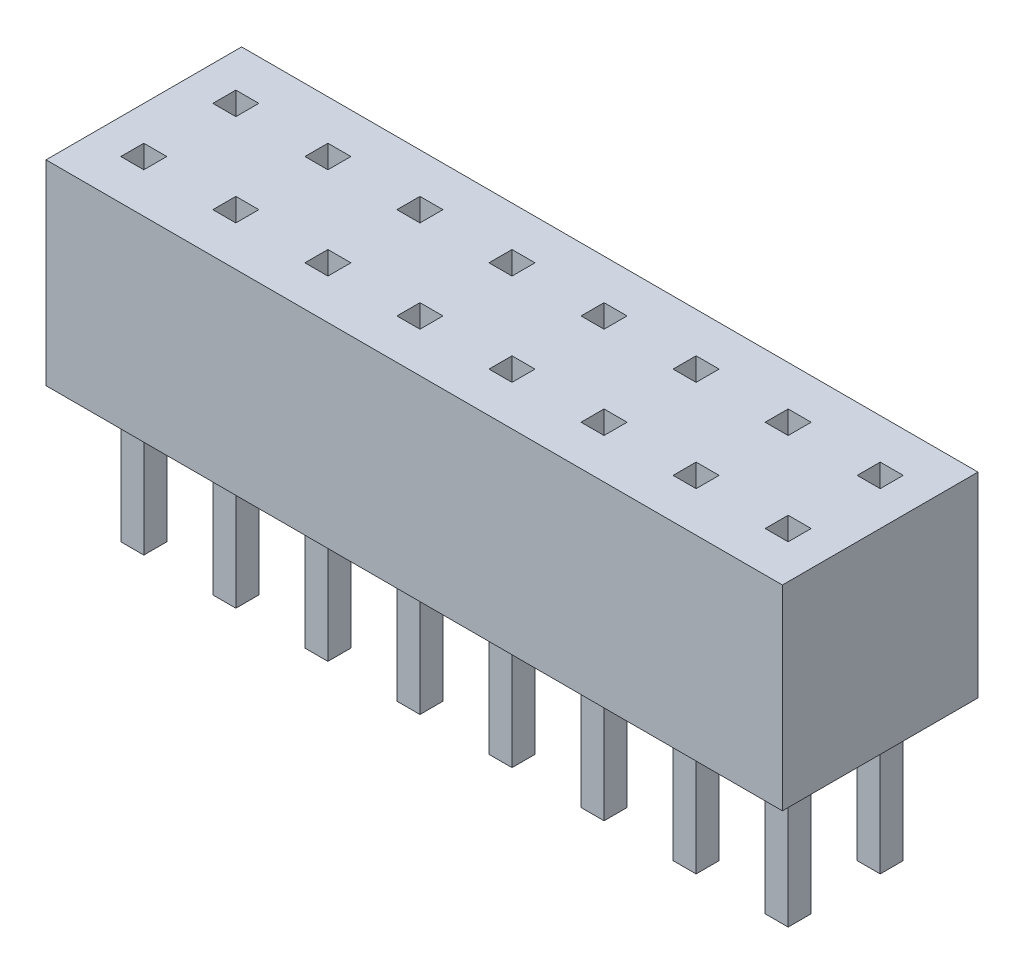
SolidWorks part; units mm, degrees
ref_plane "Front Plane" through (0, 0, 0) normal (0, 0, 1) x (1, 0, 0)
ref_plane "Top Plane" through (0, 0, 0) normal (0, 1, 0) x (1, 0, 0)
ref_plane "Right Plane" through (0, 0, 0) normal (1, 0, 0) x (0, 0, -1)
sketch "Sketch1" plane through (0, 0, 0) normal (0, 1, 0) x (1, 0, 0)
  line L1 (0, 0) -> (16, 0)
  line L2 (0, 0) -> (0, -4.25)
  line L3 (0, -4.25) -> (16, -4.25)
  line L4 (16, 0) -> (16, -4.25)
extrude "Boss-Extrude1" add sketch "Sketch1" along normal blind 4.25
sketch "Sketch3" plane through (0, 0, 0) normal (0, -1, 0) x (1, 0, 0)
  line L0 (2.75, 0.875) -> (3.25, 0.875)
  line L1 (0.75, 0.875) -> (1.25, 0.875)
  line L2 (0.75, 0.875) -> (0.75, 1.375)
  line L3 (0.75, 1.375) -> (1.25, 1.375)
  line L4 (1.25, 0.875) -> (1.25, 1.375)
  line L5 (2.75, 0.875) -> (2.75, 1.375)
  line L6 (2.75, 1.375) -> (3.25, 1.375)
  line L7 (3.25, 0.875) -> (3.25, 1.375)
  line L8 (4.75, 0.875) -> (5.25, 0.875)
  line L9 (4.75, 0.875) -> (4.75, 1.375)
  line L10 (4.75, 1.375) -> (5.25, 1.375)
  line L11 (5.25, 0.875) -> (5.25, 1.375)
  line L12 (6.75, 0.875) -> (7.25, 0.875)
  line L13 (6.75, 0.875) -> (6.75, 1.375)
  line L14 (6.75, 1.375) -> (7.25, 1.375)
  line L15 (7.25, 0.875) -> (7.25, 1.375)
  line L16 (8.75, 0.875) -> (9.25, 0.875)
  line L17 (8.75, 0.875) -> (8.75, 1.375)
  line L18 (8.75, 1.375) -> (9.25, 1.375)
  line L19 (9.25, 0.875) -> (9.25, 1.375)
  line L20 (10.75, 0.875) -> (11.25, 0.875)
  line L21 (10.75, 0.875) -> (10.75, 1.375)
  line L22 (10.75, 1.375) -> (11.25, 1.375)
  line L23 (11.25, 0.875) -> (11.25, 1.375)
  line L24 (12.75, 0.875) -> (13.25, 0.875)
  line L25 (12.75, 0.875) -> (12.75, 1.375)
  line L26 (12.75, 1.375) -> (13.25, 1.375)
  line L27 (13.25, 0.875) -> (13.25, 1.375)
  line L28 (14.75, 0.875) -> (15.25, 0.875)
  line L29 (14.75, 0.875) -> (14.75, 1.375)
  line L30 (14.75, 1.375) -> (15.25, 1.375)
  line L31 (15.25, 0.875) -> (15.25, 1.375)
  line L72 (0.75, 2.875) -> (1.25, 2.875)
  line L73 (0.75, 2.875) -> (0.75, 3.375)
  line L74 (0.75, 3.375) -> (1.25, 3.375)
  line L75 (1.25, 2.875) -> (1.25, 3.375)
  line L76 (2.75, 2.875) -> (3.25, 2.875)
  line L77 (2.75, 2.875) -> (2.75, 3.375)
  line L78 (2.75, 3.375) -> (3.25, 3.375)
  line L79 (3.25, 2.875) -> (3.25, 3.375)
  line L80 (4.75, 2.875) -> (5.25, 2.875)
  line L81 (4.75, 2.875) -> (4.75, 3.375)
  line L82 (4.75, 3.375) -> (5.25, 3.375)
  line L83 (5.25, 2.875) -> (5.25, 3.375)
  line L84 (6.75, 2.875) -> (7.25, 2.875)
  line L85 (6.75, 2.875) -> (6.75, 3.375)
  line L86 (6.75, 3.375) -> (7.25, 3.375)
  line L87 (7.25, 2.875) -> (7.25, 3.375)
  line L88 (8.75, 2.875) -> (9.25, 2.875)
  line L89 (8.75, 2.875) -> (8.75, 3.375)
  line L90 (8.75, 3.375) -> (9.25, 3.375)
  line L91 (9.25, 2.875) -> (9.25, 3.375)
  line L92 (10.75, 2.875) -> (11.25, 2.875)
  line L93 (10.75, 2.875) -> (10.75, 3.375)
  line L94 (10.75, 3.375) -> (11.25, 3.375)
  line L95 (11.25, 2.875) -> (11.25, 3.375)
  line L96 (12.75, 2.875) -> (13.25, 2.875)
  line L97 (12.75, 2.875) -> (12.75, 3.375)
  line L98 (12.75, 3.375) -> (13.25, 3.375)
  line L99 (13.25, 2.875) -> (13.25, 3.375)
  line L100 (14.75, 2.875) -> (15.25, 2.875)
  line L101 (14.75, 2.875) -> (14.75, 3.375)
  line L102 (14.75, 3.375) -> (15.25, 3.375)
  line L103 (15.25, 2.875) -> (15.25, 3.375)
  dimension "D2" = 2
  dimension "D1" = 8
extrude "Boss-Extrude2" add sketch "Sketch3" along normal blind 3
sketch "Sketch4" plane through (0, 4.25, 0) normal (0, 1, 0) x (-1, 0, 0)
  line L40 (-15.25, 0.875) -> (-14.75, 0.875)
  line L41 (-15.25, 0.875) -> (-15.25, 1.375)
  line L42 (-15.25, 1.375) -> (-14.75, 1.375)
  line L43 (-14.75, 0.875) -> (-14.75, 1.375)
  line L44 (-13.25, 0.875) -> (-12.75, 0.875)
  line L45 (-13.25, 0.875) -> (-13.25, 1.375)
  line L46 (-13.25, 1.375) -> (-12.75, 1.375)
  line L47 (-12.75, 0.875) -> (-12.75, 1.375)
  line L48 (-11.25, 0.875) -> (-10.75, 0.875)
  line L49 (-11.25, 0.875) -> (-11.25, 1.375)
  line L50 (-11.25, 1.375) -> (-10.75, 1.375)
  line L51 (-10.75, 0.875) -> (-10.75, 1.375)
  line L52 (-9.25, 0.875) -> (-8.75, 0.875)
  line L53 (-9.25, 0.875) -> (-9.25, 1.375)
  line L54 (-9.25, 1.375) -> (-8.75, 1.375)
  line L55 (-8.75, 0.875) -> (-8.75, 1.375)
  line L56 (-7.25, 0.875) -> (-6.75, 0.875)
  line L57 (-7.25, 0.875) -> (-7.25, 1.375)
  line L58 (-7.25, 1.375) -> (-6.75, 1.375)
  line L59 (-6.75, 0.875) -> (-6.75, 1.375)
  line L60 (-5.25, 0.875) -> (-4.75, 0.875)
  line L61 (-5.25, 0.875) -> (-5.25, 1.375)
  line L62 (-5.25, 1.375) -> (-4.75, 1.375)
  line L63 (-4.75, 0.875) -> (-4.75, 1.375)
  line L64 (-3.25, 0.875) -> (-2.75, 0.875)
  line L65 (-3.25, 0.875) -> (-3.25, 1.375)
  line L66 (-3.25, 1.375) -> (-2.75, 1.375)
  line L67 (-2.75, 0.875) -> (-2.75, 1.375)
  line L68 (-1.25, 0.875) -> (-0.75, 0.875)
  line L69 (-1.25, 0.875) -> (-1.25, 1.375)
  line L70 (-1.25, 1.375) -> (-0.75, 1.375)
  line L71 (-0.75, 0.875) -> (-0.75, 1.375)
  line L112 (-15.25, 2.875) -> (-14.75, 2.875)
  line L113 (-15.25, 2.875) -> (-15.25, 3.375)
  line L114 (-15.25, 3.375) -> (-14.75, 3.375)
  line L115 (-14.75, 2.875) -> (-14.75, 3.375)
  line L116 (-13.25, 2.875) -> (-12.75, 2.875)
  line L117 (-13.25, 2.875) -> (-13.25, 3.375)
  line L118 (-13.25, 3.375) -> (-12.75, 3.375)
  line L119 (-12.75, 2.875) -> (-12.75, 3.375)
  line L120 (-11.25, 2.875) -> (-10.75, 2.875)
  line L121 (-11.25, 2.875) -> (-11.25, 3.375)
  line L122 (-11.25, 3.375) -> (-10.75, 3.375)
  line L123 (-10.75, 2.875) -> (-10.75, 3.375)
  line L124 (-9.25, 2.875) -> (-8.75, 2.875)
  line L125 (-9.25, 2.875) -> (-9.25, 3.375)
  line L126 (-9.25, 3.375) -> (-8.75, 3.375)
  line L127 (-8.75, 2.875) -> (-8.75, 3.375)
  line L128 (-7.25, 2.875) -> (-6.75, 2.875)
  line L129 (-7.25, 2.875) -> (-7.25, 3.375)
  line L130 (-7.25, 3.375) -> (-6.75, 3.375)
  line L131 (-6.75, 2.875) -> (-6.75, 3.375)
  line L132 (-5.25, 2.875) -> (-4.75, 2.875)
  line L133 (-5.25, 2.875) -> (-5.25, 3.375)
  line L134 (-5.25, 3.375) -> (-4.75, 3.375)
  line L135 (-4.75, 2.875) -> (-4.75, 3.375)
  line L137 (-3.25, 2.875) -> (-2.75, 2.875)
  line L138 (-3.25, 2.875) -> (-3.25, 3.375)
  line L139 (-3.25, 3.375) -> (-2.75, 3.375)
  line L140 (-2.75, 2.875) -> (-2.75, 3.375)
  line L141 (-1.25, 2.875) -> (-0.75, 2.875)
  line L142 (-1.25, 2.875) -> (-1.25, 3.375)
  line L143 (-1.25, 3.375) -> (-0.75, 3.375)
  line L144 (-0.75, 2.875) -> (-0.75, 3.375)
  line L145 (-33.25, 0.875) -> (-32.75, 0.875)
  line L146 (-35.25, 0.875) -> (-34.75, 0.875)
  line L147 (-35.25, 0.875) -> (-35.25, 1.375)
  line L148 (-35.25, 1.375) -> (-34.75, 1.375)
  line L149 (-34.75, 0.875) -> (-34.75, 1.375)
  line L150 (-33.25, 0.875) -> (-33.25, 1.375)
  line L151 (-33.25, 1.375) -> (-32.75, 1.375)
  line L152 (-32.75, 0.875) -> (-32.75, 1.375)
  line L153 (-31.25, 0.875) -> (-30.75, 0.875)
  line L154 (-31.25, 0.875) -> (-31.25, 1.375)
  line L155 (-31.25, 1.375) -> (-30.75, 1.375)
  line L156 (-30.75, 0.875) -> (-30.75, 1.375)
  line L157 (-29.25, 0.875) -> (-28.75, 0.875)
  line L158 (-29.25, 0.875) -> (-29.25, 1.375)
  line L159 (-29.25, 1.375) -> (-28.75, 1.375)
  line L160 (-28.75, 0.875) -> (-28.75, 1.375)
  line L161 (-27.25, 0.875) -> (-26.75, 0.875)
  line L162 (-27.25, 0.875) -> (-27.25, 1.375)
  line L163 (-27.25, 1.375) -> (-26.75, 1.375)
  line L164 (-26.75, 0.875) -> (-26.75, 1.375)
  line L165 (-25.25, 0.875) -> (-24.75, 0.875)
  line L166 (-25.25, 0.875) -> (-25.25, 1.375)
  line L167 (-25.25, 1.375) -> (-24.75, 1.375)
  line L168 (-24.75, 0.875) -> (-24.75, 1.375)
  line L169 (-23.25, 0.875) -> (-22.75, 0.875)
  line L170 (-23.25, 0.875) -> (-23.25, 1.375)
  line L171 (-23.25, 1.375) -> (-22.75, 1.375)
  line L172 (-22.75, 0.875) -> (-22.75, 1.375)
  line L173 (-21.25, 0.875) -> (-20.75, 0.875)
  line L174 (-21.25, 0.875) -> (-21.25, 1.375)
  line L175 (-21.25, 1.375) -> (-20.75, 1.375)
  line L176 (-20.75, 0.875) -> (-20.75, 1.375)
  line L177 (-19.25, 0.875) -> (-18.75, 0.875)
  line L178 (-19.25, 0.875) -> (-19.25, 1.375)
  line L179 (-19.25, 1.375) -> (-18.75, 1.375)
  line L180 (-18.75, 0.875) -> (-18.75, 1.375)
  line L181 (-17.25, 0.875) -> (-16.75, 0.875)
  line L182 (-17.25, 0.875) -> (-17.25, 1.375)
  line L183 (-17.25, 1.375) -> (-16.75, 1.375)
  line L184 (-16.75, 0.875) -> (-16.75, 1.375)
  line L185 (-35.25, 2.875) -> (-34.75, 2.875)
  line L186 (-35.25, 2.875) -> (-35.25, 3.375)
  line L187 (-35.25, 3.375) -> (-34.75, 3.375)
  line L188 (-34.75, 2.875) -> (-34.75, 3.375)
  line L189 (-33.25, 2.875) -> (-32.75, 2.875)
  line L190 (-33.25, 2.875) -> (-33.25, 3.375)
  line L191 (-33.25, 3.375) -> (-32.75, 3.375)
  line L192 (-32.75, 2.875) -> (-32.75, 3.375)
  line L193 (-31.25, 2.875) -> (-30.75, 2.875)
  line L194 (-31.25, 2.875) -> (-31.25, 3.375)
  line L195 (-31.25, 3.375) -> (-30.75, 3.375)
  line L196 (-30.75, 2.875) -> (-30.75, 3.375)
  line L197 (-29.25, 2.875) -> (-28.75, 2.875)
  line L198 (-29.25, 2.875) -> (-29.25, 3.375)
  line L199 (-29.25, 3.375) -> (-28.75, 3.375)
  line L200 (-28.75, 2.875) -> (-28.75, 3.375)
  line L201 (-27.25, 2.875) -> (-26.75, 2.875)
  line L202 (-27.25, 2.875) -> (-27.25, 3.375)
  line L203 (-27.25, 3.375) -> (-26.75, 3.375)
  line L204 (-26.75, 2.875) -> (-26.75, 3.375)
  line L205 (-25.25, 2.875) -> (-24.75, 2.875)
  line L206 (-25.25, 2.875) -> (-25.25, 3.375)
  line L207 (-25.25, 3.375) -> (-24.75, 3.375)
  line L208 (-24.75, 2.875) -> (-24.75, 3.375)
  line L209 (-23.25, 2.875) -> (-22.75, 2.875)
  line L210 (-23.25, 2.875) -> (-23.25, 3.375)
  line L211 (-23.25, 3.375) -> (-22.75, 3.375)
  line L212 (-22.75, 2.875) -> (-22.75, 3.375)
  line L213 (-21.25, 2.875) -> (-20.75, 2.875)
  line L214 (-21.25, 2.875) -> (-21.25, 3.375)
  line L215 (-21.25, 3.375) -> (-20.75, 3.375)
  line L216 (-20.75, 2.875) -> (-20.75, 3.375)
  line L217 (-19.25, 2.875) -> (-18.75, 2.875)
  line L218 (-19.25, 2.875) -> (-19.25, 3.375)
  line L219 (-19.25, 3.375) -> (-18.75, 3.375)
  line L220 (-18.75, 2.875) -> (-18.75, 3.375)
  line L221 (-17.25, 2.875) -> (-16.75, 2.875)
  line L222 (-17.25, 2.875) -> (-17.25, 3.375)
  line L223 (-17.25, 3.375) -> (-16.75, 3.375)
  line L224 (-16.75, 2.875) -> (-16.75, 3.375)
  dimension "D2" = 17
extrude "Cut-Extrude1" cut sketch "Sketch4" against normal blind 4
